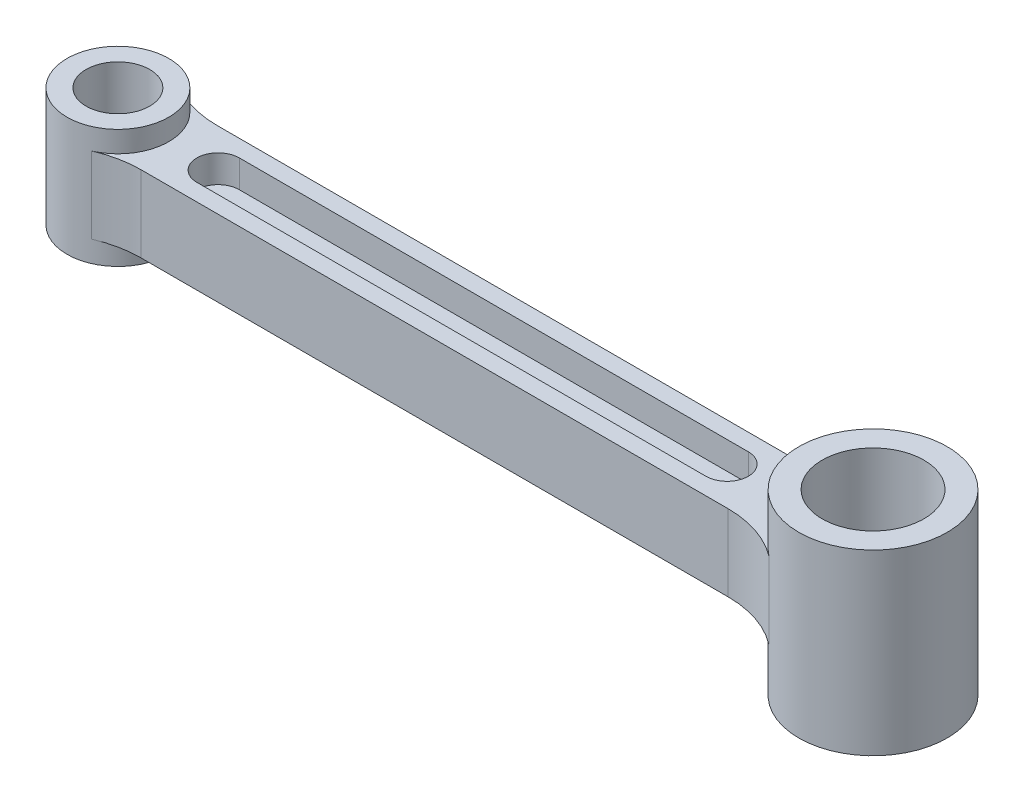
SolidWorks part; units mm, degrees
ref_plane "Front Plane" through (0, 0, 0) normal (0, 0, 1) x (1, 0, 0)
ref_plane "Top Plane" through (0, 0, 0) normal (0, 1, 0) x (1, 0, 0)
ref_plane "Right Plane" through (0, 0, 0) normal (1, 0, 0) x (0, 0, -1)
sketch "Sketch1" plane through (0, 0, 0) normal (0, 1, 0) x (1, 0, 0)
  line L0 (0, 0) -> (178, 0) construction
  circle A0 centre (0, 0) radius 7.5
  circle A1 centre (0, 0) radius 12
  circle A2 centre (178, 0) radius 12
  circle A3 centre (178, 0) radius 17.5
  dimension "D2" = 24
  dimension "D3" = 15
  dimension "D4" = 24
  dimension "D5" = 35
  dimension "D1" = 178
extrude "Boss-Extrude1" add sketch "Sketch1" along normal mid plane 42 contours A2 | A3
extrude "Boss-Extrude2" add sketch "Sketch1<5>" along normal mid plane 28 separate body contours A0 | A1
sketch "Sketch1<5>" plane through (0, 0, 0) normal (0, 1, 0) x (1, 0, 0) same geometry as "Sketch1"
sketch "Sketch2" plane through (0, 0, 0) normal (0, 1, 0) x (1, 0, 0)
  line L0 (7.9373, 9) -> (162.9917, 9)
  line L1 (0, 0) -> (178, 0) construction
  line L2 (7.9373, -9) -> (162.9917, -9)
  circle A1 centre (178, 0) radius 17.5 construction
  circle A3 centre (0, 0) radius 12 construction
  arc A5 (162.9917, 9) -> (162.9917, -9) centre (178, 0) ccw
  arc A7 (7.9373, -9) -> (7.9373, 9) centre (0, 0) ccw
  dimension "D1" = 9
  dimension "D2" = 18
  dimension "D3" = 155.0544
extrude "Boss-Extrude3" add sketch "Sketch2" along normal mid plane 18
fillet "Fillet2" radius 24 4 edges at (162.9917, 0, 9) (162.9917, 0, -9) (7.9373, 0, -9) (7.9373, 0, 9)
sketch "Sketch4" plane through (0, 0, 0) normal (0, 1, 0) x (1, 0, 0)
  line L0 (152.8355, 9) -> (14.3875, 9) construction
  line L1 (18.6115, 5) -> (148.6115, 5)
  line L2 (18.6115, 5) -> (18.6115, -5)
  line L3 (18.6115, -5) -> (148.6115, -5)
  line L4 (148.6115, 5) -> (148.6115, -5)
  line L5 (18.6115, 5) -> (148.6115, -5) construction
  line L6 (18.6115, -5) -> (148.6115, 5) construction
  point P0 (83.6115, 0)
  point P7 (83.6115, 9)
  dimension "D1" = 130
  dimension "D2" = 10
extrude "Cut-Extrude1" cut sketch "Sketch4" against normal blind 18 from offset 2.5 offset against normal yes
mirror "Mirror1" about plane through (0, 0, 0) normal (0, 1, 0) of "Cut-Extrude1"
fillet "Fillet4" 2 edges at (18.6115, 5.75, -5) (18.6115, 5.75, 5) type full round first side face at (83.6115, 5.75, -5) second side face at (83.6115, 5.75, 5) middle face at (18.6115, 5.75, 0)
fillet "Fillet5" 2 edges at (148.6115, 5.75, -5) (148.6115, 5.75, 5) type full round first side face at (86.1115, 5.75, -5) second side face at (86.1115, 5.75, 5) middle face at (148.6115, 5.75, 0)
fillet "Fillet6" 2 edges at (18.6115, -5.75, 5) (18.6115, -5.75, -5) type full round first side face at (83.6115, -5.75, 5) second side face at (83.6115, -5.75, -5) middle face at (18.6115, -5.75, 0)
fillet "Fillet7" 2 edges at (148.6115, -5.75, 5) (148.6115, -5.75, -5) type full round first side face at (86.1115, -5.75, 5) second side face at (86.1115, -5.75, -5) middle face at (148.6115, -5.75, 0)
